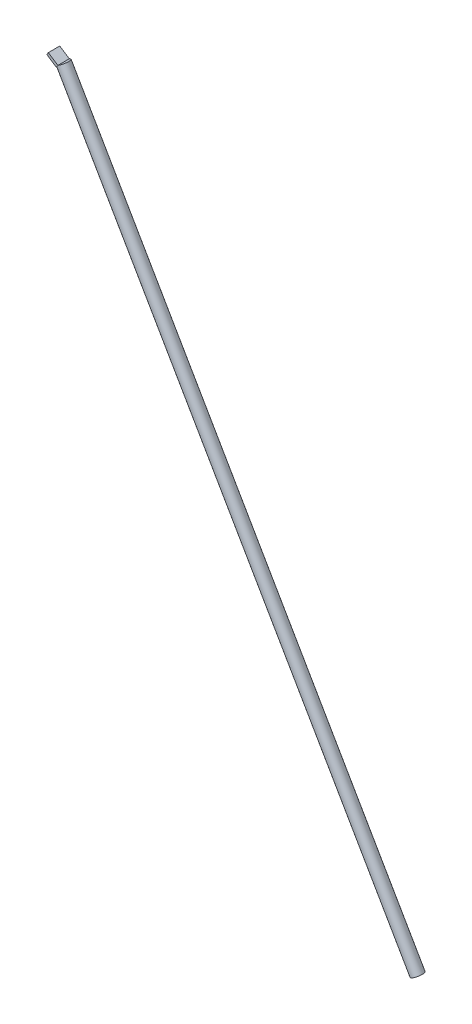
SolidWorks part; units mm, degrees
ref_plane "Front Plane" through (0, 0, 0) normal (0, 0, 1) x (1, 0, 0)
ref_plane "Top Plane" through (0, 0, 0) normal (0, 1, 0) x (1, 0, 0)
ref_plane "Right Plane" through (0, 0, 0) normal (1, 0, 0) x (0, 0, -1)
sketch "Sketch1" plane through (0, 0, 0) normal (0, 0, 1) x (1, 0, 0)
  line L0 (0, 0) -> (0, 17.4992) construction
  line L1 (0, 0) -> (-16.6893, 11.0213)
  line L2 (-8.3446, 5.5106) -> (-11.1, 1.3383) construction
  line L3 (-16.6893, 11.0213) -> (-19.4446, 6.849)
  line L4 (-19.4446, 6.849) -> (-11.1, 1.3383)
  line L5 (-11.1, 1.3383) -> (-2.7553, -4.1723)
  line L6 (-2.7553, -4.1723) -> (0, 0)
  dimension "D1" = 20
  dimension "D2" = 56.56
  dimension "D3" = 10
extrude "Boss-Extrude1" add sketch "Sketch1" along normal blind 20
ref_axis "Axis1" through (0, 0, -1) along (0, 0, 1)
sketch "Sketch2" plane through (0, 0, 0) normal (0, 0, 1) x (1, 0, 0)
  line L0 (-1.3777, -2.0862) -> (-0.7923, -3.1) construction
  line L1 (-2.7553, -4.1723) -> (0, 0) construction
  line L2 (0, 0) -> (0, 5.2498) construction
  dimension "D1" = 150
ref_plane "Plane4" through (0, 0, 0) normal (0.5, -0.866, 0) x (-0.866, -0.5, 0)
sketch "Sketch3" plane through (0, 0, 0) normal (0.5, -0.866, 0) x (-0.866, -0.5, 0)
  line L0 (0, 0) -> (0, -10) construction
  line L1 (0, -20) -> (0, 0) construction
  circle A0 centre (0, -10) radius 10
extrude "Boss-Extrude2" add sketch "Sketch3" along normal blind 1240
